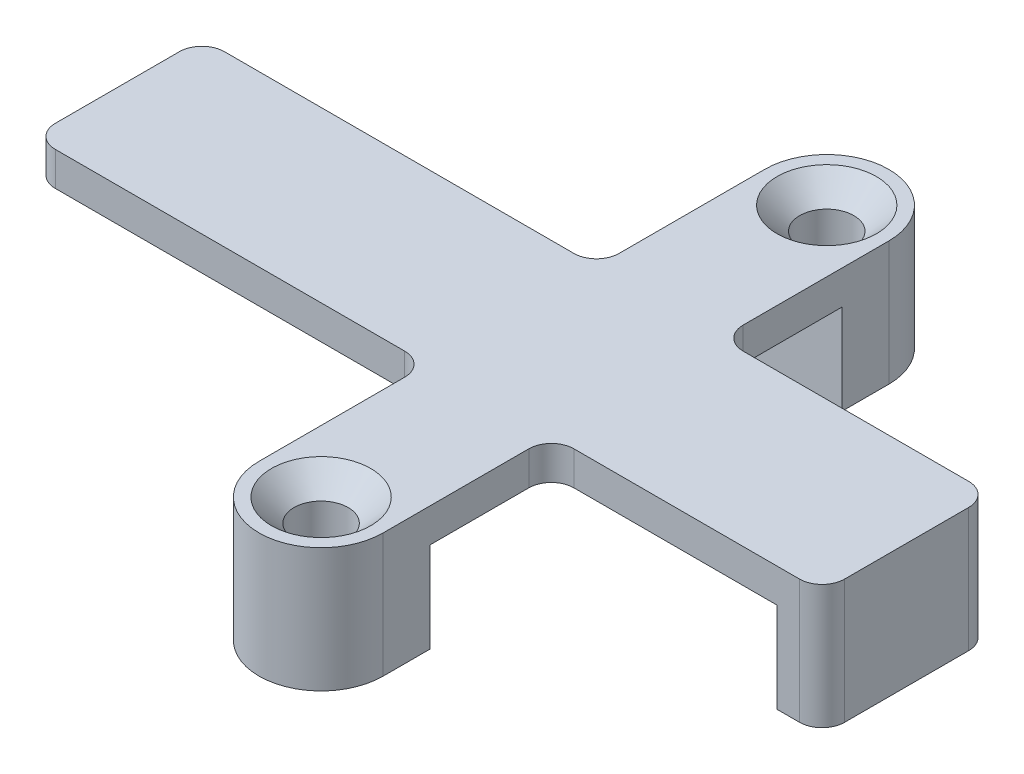
SolidWorks part; units mm, degrees
ref_plane "Front Plane" through (0, 0, 0) normal (0, 0, 1) x (1, 0, 0)
ref_plane "Top Plane" through (0, 0, 0) normal (0, 1, 0) x (1, 0, 0)
ref_plane "Right Plane" through (0, 0, 0) normal (1, 0, 0) x (0, 0, -1)
sketch "Sketch1" plane through (0, 0, 0) normal (0, 1, 0) x (1, 0, 0)
  line L0 (0, 11.2072) -> (0, -11.2072) construction
  line L1 (0, 11.2072) -> (0, -11.2072) construction
  line L2 (2.75, 11.2072) -> (2.75, -11.2072)
  line L3 (-2.75, 11.2072) -> (-2.75, -11.2072)
  line L4 (12.75, 0) -> (-20.24, 0) construction
  line L5 (12.75, 3.75) -> (-20.24, 3.75)
  line L6 (12.75, 3.75) -> (12.75, -3.75)
  line L7 (12.75, -3.75) -> (-20.24, -3.75)
  line L8 (-20.24, 3.75) -> (-20.24, -3.75)
  line L9 (2.75, 9.125) -> (-2.75, 9.125)
  line L10 (12.75, 3.75) -> (14.75, 3.75)
  line L11 (12.75, 3.75) -> (12.75, -3.75)
  line L12 (12.75, -3.75) -> (14.75, -3.75)
  line L13 (14.75, 3.75) -> (14.75, -3.75)
  line L14 (12.75, 9) -> (-20.24, 9) construction
  line L15 (12.75, 9) -> (12.75, -9) construction
  line L16 (12.75, -9) -> (-20.24, -9) construction
  line L17 (-20.24, 9) -> (-20.24, -9) construction
  line L18 (2.75, -9.125) -> (-2.75, -9.125)
  arc A0 (2.75, 11.2072) -> (-2.75, 11.2072) centre (0, 11.2072) ccw
  arc A1 (-2.75, -11.2072) -> (2.75, -11.2072) centre (0, -11.2072) ccw
  circle A2 centre (0, 11.2072) radius 1.75
  circle A3 centre (0, -11.2072) radius 1.75
  point P2 (0, 0)
  point P4 (0, 0)
  point P25 (12.75, 0)
  dimension "D2" = 1
  dimension "D3" = 3.5
  dimension "D1" = 22.4144
  dimension "D4" = 12.75
  dimension "D5" = 7.5
  dimension "D6" = 20.24
  dimension "D7" = 2
  dimension "D8" = 18
  dimension "D9" = 0.125
extrude "Boss-Extrude1" add sketch "Sketch1" along normal blind 1.5 contours L13 L10 L6 L12 | L7 L6 L5 L2 | L7 L2 L5 L3 | L5 L8 L7 L3 | L18 L2 L7 L3 | L2 L9 L3 L5 | L2 A0 L3 L9 A2 | A2 | L3 A1 L2 L18 A3 | A3 region at (2.6768, 0, -10.1661) region at (0, 0, -6.4375) region at (7.75, 0, 0) region at (0, 0, 0) region at (0, 0, 6.4375) region at (13.75, 0, 0) region at (-11.495, 0, 0) region at (2.6768, 0, 10.1661) region at (0, 0, -11.2072) region at (0, 0, 11.2072)
extrude "Boss-Extrude2" add sketch "Sketch1<4>" against normal blind 4 contours L2 A0 L3 L9 A2 | L3 A1 L2 L18 A3 | L13 L10 L6 L12 | A2 | A3 region at (2.6768, 0, -10.1661) region at (13.75, 0, 0) region at (2.6768, 0, 10.1661) region at (0, 0, -11.2072) region at (0, 0, 11.2072)
sketch "Sketch1<4>" plane through (0, 0, 0) normal (0, 1, 0) x (1, 0, 0) same geometry as "Sketch1"
hole_wizard "CSK for M2 Flat Head Machine Screw1" positions "3DSketch1" profile "Sketch3" countersink size "M2" standard "ANSI Metric" end condition through all
sketch3d "3DSketch1"
  circle A0 centre (0, 0, 11.2072) radius 1.75 construction
  circle A1 centre (0, 0, -11.2072) radius 1.75 construction
  point P0 (0, 0, -11.2072)
  point P3 (0, 0, 11.2072)
  point P6 (0, 1.5, -11.2072)
  point P8 (0, 1.5, 11.2072)
  point P11 (0, 0, 0)
  point P14 (0, 1.75, 11.2072)
  point P15 (0, 0, 0)
  point P18 (0, 1.75, -11.2072)
sketch "Sketch3" plane through (0, 1.5, 11.2072) normal (1, 0, 0) x (0, 0, 1)
  line L0 (0, 0) -> (0, 5.5)
  line L1 (0, 5.5) -> (1.2, 5.5)
  line L2 (1.2, 5.5) -> (1.2, 1)
  line L3 (1.2, 1) -> (2.2, 0)
  line L5 (2.2, 0) -> (0, 0)
  line L6 (-1.2, 1) -> (-2.2, 0) construction
  line L11 (0, -6.35) -> (0, 107.95) construction
  dimension "Thru Hole Dia." = 2.4
  dimension "Thru Hole Depth" = 5.5
  dimension "Near C'Sink Dia." = 4.4
  dimension "Near C'Sink Angle" = 90
fillet "Fillet1" radius 1 8 edges at (14.75, -1.25, 3.75) (2.75, 0.75, 3.75) (-2.75, 0.75, 3.75) (-20.24, 0.75, 3.75) (-20.24, 0.75, -3.75) (2.75, 0.75, -3.75) (14.75, -1.25, -3.75) (-2.75, 0.75, -3.75)
